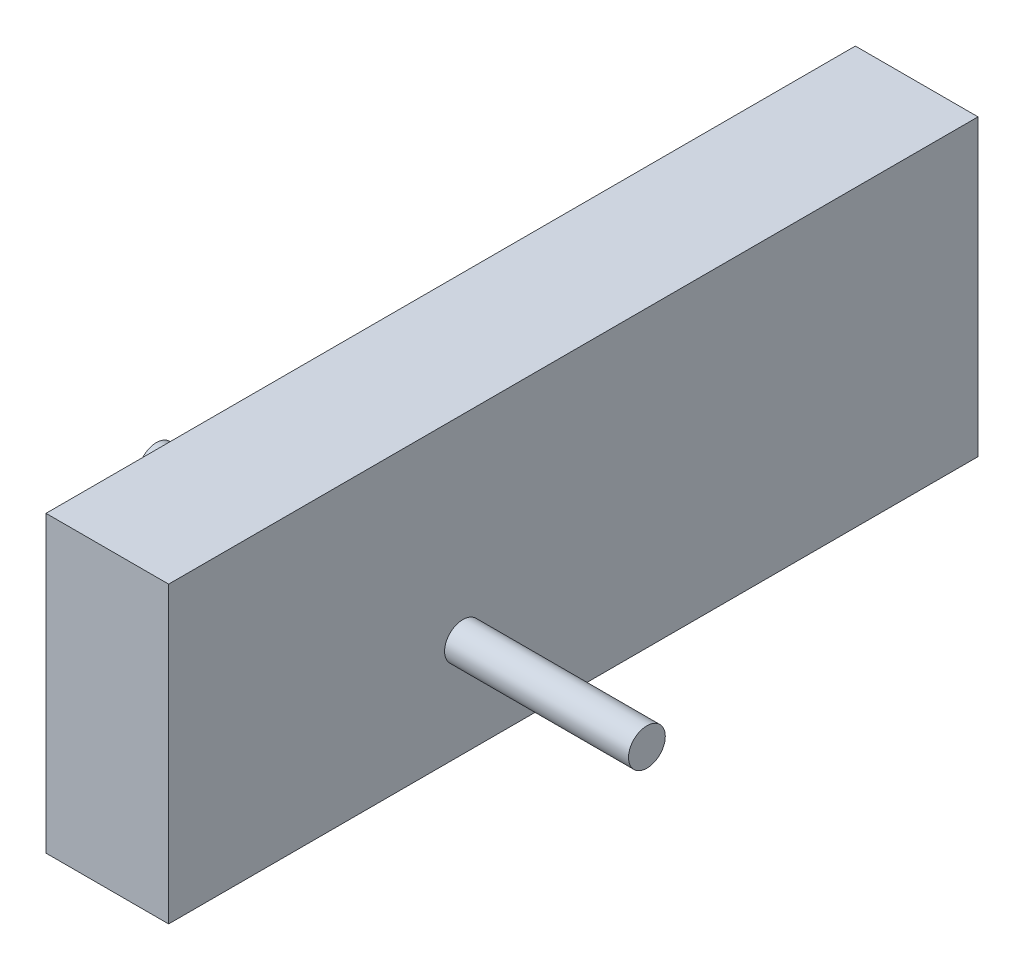
SolidWorks part; units mm, degrees
material "Custom Plastic"
ref_plane "Front Plane" through (0, 0, 0) normal (0, 0, 1) x (1, 0, 0)
ref_plane "Top Plane" through (0, 0, 0) normal (0, 1, 0) x (1, 0, 0)
ref_plane "Right Plane" through (0, 0, 0) normal (1, 0, 0) x (0, 0, -1)
sketch "Sketch1" plane through (0, 0, 0) normal (1, 0, 0) x (0, 0, -1)
  circle A0 centre (0, 0) radius 9.525
  dimension "D1" = 19.05
extrude "Boss-Extrude1" add sketch "Sketch1" along normal mid plane 254
sketch "Sketch2" plane through (0, 0, 0) normal (1, 0, 0) x (0, 0, -1)
  line L1 (-152.4, -50.8) -> (266.7, -50.8)
  line L2 (-152.4, -50.8) -> (-152.4, 101.6)
  line L3 (-152.4, 101.6) -> (266.7, 101.6)
  line L4 (266.7, -50.8) -> (266.7, 101.6)
  dimension "D1" = 152.4
  dimension "D2" = 419.1
  dimension "D3" = 50.8
  dimension "D4" = 152.4
extrude "Boss-Extrude2" add sketch "Sketch2" along normal mid plane 63.5
